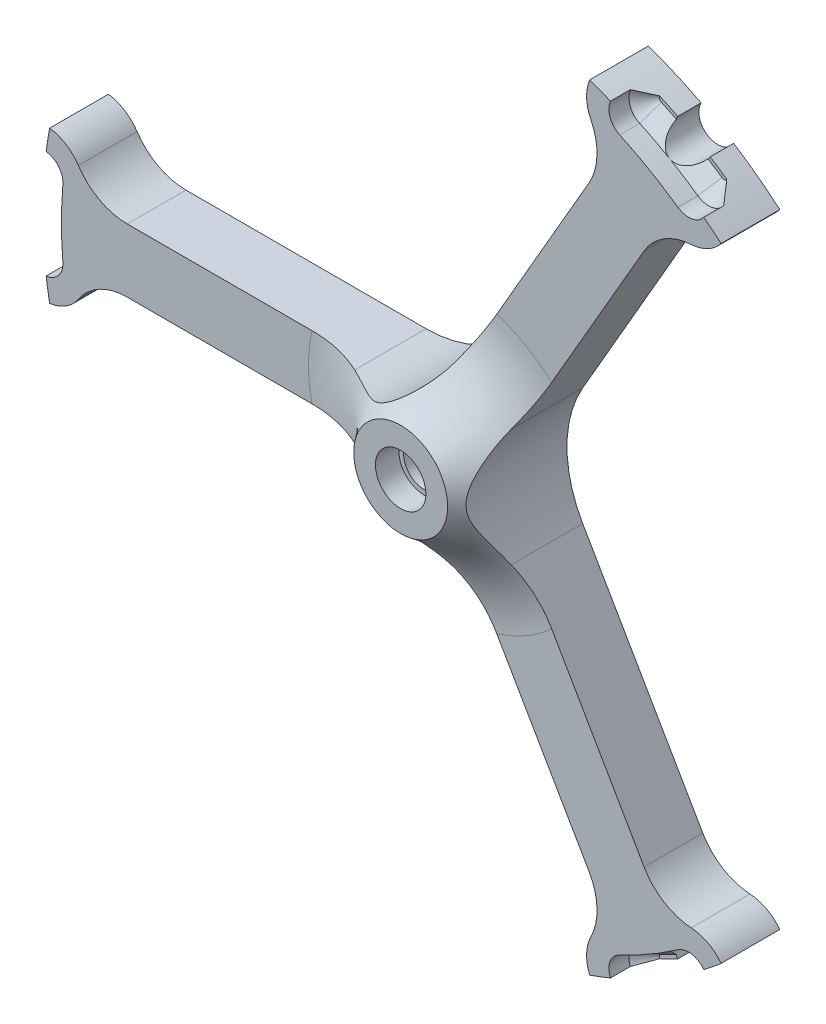
SolidWorks part; units mm, degrees
ref_plane "Plan de face" through (0, 0, 0) normal (0, 0, 1) x (1, 0, 0)
ref_plane "Plan de dessus" through (0, 0, 0) normal (0, 1, 0) x (1, 0, 0)
ref_plane "Plan de droite" through (0, 0, 0) normal (1, 0, 0) x (0, 0, -1)
sketch "Esquisse1" plane through (0, 0, 0) normal (0, 0, 1) x (1, 0, 0)
  line L19 (-1000, 0) -> (49000, 0) construction
  line L21 (-27.7888, 2.7) -> (-7.3323, 2.7)
  line L23 (-27.7888, -2.7) -> (-7.3323, -2.7)
  line L33 (16.2327, 22.7158) -> (6.0044, 5)
  line L34 (11.5561, 25.4158) -> (1.3279, 7.7)
  line L35 (11.5561, -25.4158) -> (1.3279, -7.7)
  line L36 (16.2327, -22.7158) -> (6.0044, -5)
  arc A0 (-34.3972, 6.4678) -> (-34.6976, 4.5906) centre (0, 0) ccw
  arc A7 (-33.2771, 2.8629) -> (-34.6976, 4.5906) centre (-34.8712, 3) ccw
  arc A8 (-33.2771, -2.8629) -> (-34.6976, -4.5906) centre (-34.8712, -3) cw
  arc A12 (-33.2771, 2.8629) -> (-33.2771, -2.8629) centre (0, 0) ccw
  arc A13 (-31.9549, 4.9353) -> (-34.3972, 6.4678) centre (-34.8712, 3) ccw
  arc A14 (-31.9549, -4.9353) -> (-34.3972, -6.4678) centre (-34.8712, -3) cw
  arc A15 (-34.6976, -4.5906) -> (-34.3972, -6.4678) centre (0, 0) ccw
  arc A16 (-27.7888, -2.7) -> (-31.9549, -4.9353) centre (-27.7888, -7.7) ccw
  arc A17 (-27.7888, 2.7) -> (-31.9549, 4.9353) centre (-27.7888, 7.7) cw
  arc A48 (22.7998, 26.555) -> (21.3244, 27.7538) centre (0, 0) ccw
  arc A49 (19.1178, 27.3874) -> (21.3244, 27.7538) centre (20.0337, 28.6993) ccw
  arc A50 (14.1592, 30.2502) -> (13.3733, 32.3443) centre (14.8375, 31.6993) cw
  arc A51 (19.1178, 27.3874) -> (14.1592, 30.2502) centre (0, 0) ccw
  arc A52 (20.2516, 25.2061) -> (22.7998, 26.555) centre (20.0337, 28.6993) ccw
  arc A53 (11.7034, 30.1414) -> (11.5974, 33.0227) centre (14.8375, 31.6993) cw
  arc A54 (13.3733, 32.3443) -> (11.5974, 33.0227) centre (0, 0) ccw
  arc A55 (11.5561, 25.4158) -> (11.7034, 30.1414) centre (7.226, 27.9158) ccw
  arc A56 (16.2327, 22.7158) -> (20.2516, 25.2061) centre (20.5628, 20.2158) cw
  arc A57 (11.5974, -33.0227) -> (13.3733, -32.3443) centre (0, 0) ccw
  arc A58 (14.1592, -30.2502) -> (13.3733, -32.3443) centre (14.8375, -31.6993) ccw
  arc A59 (19.1178, -27.3874) -> (21.3244, -27.7538) centre (20.0337, -28.6993) cw
  arc A60 (14.1592, -30.2502) -> (19.1178, -27.3874) centre (0, 0) ccw
  arc A61 (11.7034, -30.1414) -> (11.5974, -33.0227) centre (14.8375, -31.6993) ccw
  arc A62 (20.2516, -25.2061) -> (22.7998, -26.555) centre (20.0337, -28.6993) cw
  arc A63 (21.3244, -27.7538) -> (22.7998, -26.555) centre (0, 0) ccw
  arc A64 (16.2327, -22.7158) -> (20.2516, -25.2061) centre (20.5628, -20.2158) ccw
  arc A65 (11.5561, -25.4158) -> (11.7034, -30.1414) centre (7.226, -27.9158) cw
  arc A66 (-7.3323, -2.7) -> (1.3279, -7.7) centre (-7.3323, -12.7) cw
  arc A67 (6.0044, -5) -> (6.0044, 5) centre (14.6647, 0) cw
  arc A68 (1.3279, 7.7) -> (-7.3323, 2.7) centre (-7.3323, 12.7) cw
  point P38 (0, 0)
  point P50 (3.1177, 0)
  point P55 (0, 0)
  point P56 (0, 0)
  point P80 (0, 0)
  dimension "D1" = 70
  dimension "D3" = 3
  dimension "D2" = 3.2
  dimension "D4" = 5
  dimension "D5" = 10
extrude "Boss.-Extru.1" add sketch "Esquisse1" along normal blind 5
sketch "Esquisse7" plane through (0, 0, 0) normal (0, 0, -1) x (-1, 0, 0)
  line L0 (-1000, 0) -> (49000, 0) construction
  arc A0 (34.6976, -4.5906) -> (34.6976, 4.5906) centre (0, 0) ccw
  arc A2 (33.2771, -2.8629) -> (33.2771, 2.8629) centre (0, 0) ccw
  arc A4 (34.9634, 1.5996) -> (34.9634, -1.5996) centre (35, 0) ccw
  arc A5 (34.6976, 4.5906) -> (33.2771, 2.8629) centre (34.8712, 3) ccw
  arc A6 (33.2771, -2.8629) -> (33.2771, 2.8629) centre (0, 0) ccw construction
  arc A7 (34.6976, -4.5906) -> (33.2771, -2.8629) centre (34.8712, -3) cw
  arc A8 (-21.3244, -27.7538) -> (-13.3733, -32.3443) centre (0, 0) ccw
  arc A9 (-19.1178, -27.3874) -> (-14.1592, -30.2502) centre (0, 0) ccw
  arc A10 (-16.0964, -31.079) -> (-18.867, -29.4794) centre (-17.5, -30.3109) ccw
  arc A11 (-13.3733, -32.3443) -> (-14.1592, -30.2502) centre (-14.8375, -31.6993) ccw
  arc A12 (-21.3244, -27.7538) -> (-19.1178, -27.3874) centre (-20.0337, -28.6993) cw
  arc A13 (-13.3733, 32.3443) -> (-21.3244, 27.7538) centre (0, 0) ccw
  arc A14 (-14.1592, 30.2502) -> (-19.1178, 27.3874) centre (0, 0) ccw
  arc A15 (-18.867, 29.4794) -> (-16.0964, 31.079) centre (-17.5, 30.3109) ccw
  arc A16 (-21.3244, 27.7538) -> (-19.1178, 27.3874) centre (-20.0337, 28.6993) ccw
  arc A17 (-13.3733, 32.3443) -> (-14.1592, 30.2502) centre (-14.8375, 31.6993) cw
  point P36 (0, 0)
  arc M44 (34.6976, -4.5906) -> (33.2771, -2.8629) centre (34.8712, -3) cw
  arc M45 (33.2771, -2.8629) -> (33.2771, 2.8629) centre (0, 0) ccw
  arc M46 (33.2771, 2.8629) -> (34.6976, 4.5906) centre (34.8712, 3) cw
  arc M56 (-13.3733, 32.3443) -> (-14.1592, 30.2502) centre (-14.8375, 31.6993) cw
  arc M57 (-14.1592, 30.2502) -> (-19.1178, 27.3874) centre (0, 0) ccw
  arc M58 (-19.1178, 27.3874) -> (-21.3244, 27.7538) centre (-20.0337, 28.6993) cw
  arc M68 (-21.3244, -27.7538) -> (-19.1178, -27.3874) centre (-20.0337, -28.6993) cw
  arc M69 (-19.1178, -27.3874) -> (-14.1592, -30.2502) centre (0, 0) ccw
  arc M70 (-14.1592, -30.2502) -> (-13.3733, -32.3443) centre (-14.8375, -31.6993) cw
  dimension "D1" = 3.2
  dimension "D3" = 3.2
  dimension "D4" = 70
  dimension "D2" = 3
extrude "Boss.-Extru.5" add sketch "Esquisse7" against normal blind 2 contours A4 A0 A2 M46 | A4 A0 M45 M44 | A10 A8 A9 M70 | A10 A8 M69 M68 | A15 A13 M57 M56 | A15 A13 A14 M58 region at (-34.0862, -2.7129, 0) region at (-34.0862, 2.7129, 0) region at (19.3926, -28.1631, 0) region at (14.6937, -30.876, 0) region at (14.6937, 30.876, 0) region at (19.3926, 28.1631, 0)
sketch "Esquisse4" plane through (0, 0, 5) normal (0, 0, 1) x (1, 0, 0)
  circle A1 centre (0, 0) radius 4
  dimension "D1" = 8
extrude "Boss.-Extru.3" add sketch "Esquisse4" along normal blind 4.5
sketch "Esquisse5" plane through (0, 0, 9.5) normal (0, 0, 1) x (1, 0, 0)
  circle A0 centre (0, 0) radius 2.15
  dimension "D1" = 4.3
extrude "Enlèv. mat.-Extru.2" cut sketch "Esquisse5" against normal blind 2
fillet "Congé1" radius 10 1 edges at (4, 0, 5)
sketch "Esquisse6" plane through (0, 0, 7.5) normal (0, 0, 1) x (1, 0, 0)
  circle A0 centre (0, 0) radius 1.75
  dimension "D1" = 3.5
extrude "Enlèv. mat.-Extru.3" cut sketch "Esquisse6" against normal up to next
chamfer "Chanfrein1" distance 1.3 angle 45 12 edges at (-33.6353, -4.0162, 2) (-33.3693, -1.4327, 2) (-33.6353, 4.0162, 2) (-33.3693, 1.4327, 2) (13.3395, 31.1371, 2) (15.4438, 29.615, 2) (20.2958, 27.121, 2) (17.9254, 28.1822, 2) (20.2958, -27.121, 2) (13.3395, -31.1371, 2) (15.4438, -29.615, 2) (17.9254, -28.1822, 2)
